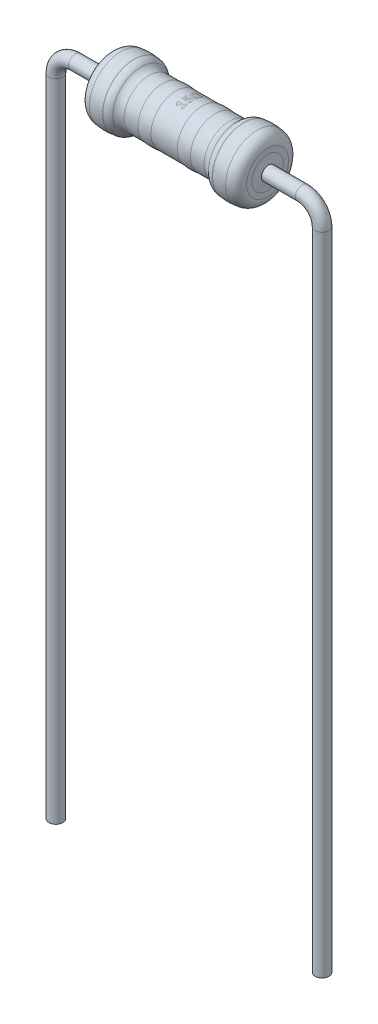
SolidWorks part; units mm, degrees
material "Plain Carbon Steel"
ref_plane "Front Plane" through (0, 0, 0) normal (0, 0, 1) x (1, 0, 0)
ref_plane "Top Plane" through (0, 0, 0) normal (0, 1, 0) x (1, 0, 0)
ref_plane "Right Plane" through (0, 0, 0) normal (1, 0, 0) x (0, 0, -1)
sketch "Sketch1" plane through (0, 0, 0) normal (0, 0, 1) x (1, 0, 0)
  line L0 (-4.33, 0) -> (4.33, 0)
  line L1 (-5.08, -0.75) -> (-5.08, -25.4)
  line L2 (5.08, -0.75) -> (5.08, -25.4)
  line L3 (-5.08, -25.4) -> (5.08, -25.4) construction
  line L4 (0, 0) -> (0, -25.4) construction
  arc A0 (-4.33, 0) -> (-5.08, -0.75) centre (-4.33, -0.75) ccw
  arc A1 (4.33, 0) -> (5.08, -0.75) centre (4.33, -0.75) cw
  dimension "D2" = 0.75
  dimension "D1" = 10.16
  dimension "D3" = 25.4
ref_plane "Plane1" through (-5.08, -25.4, 0) normal (0, -1, 0) x (-1, 0, 0)
sketch "Sketch2" plane through (-5.08, -25.4, 0) normal (0, -1, 0) x (-1, 0, 0)
  circle A0 centre (0, 0) radius 0.265
  dimension "D1" = 0.53
sweep "Sweep1" add profiles "Sketch2" path "Sketch1"
sketch "Sketch3" plane through (0, 0, 0) normal (0, 0, 1) x (1, 0, 0)
  line L0 (-3, 0) -> (3, 0)
  line L5 (-3, 0) -> (-3, 1.2)
  line L6 (3, 0) -> (3, 1.2)
  line L7 (-3, 1.2) -> (-1.75, 1.2)
  line L8 (3, 1.2) -> (1.75, 1.2)
  line L9 (-1.75, 1.2) -> (-1.75, 0.95)
  line L10 (-1.75, 0.95) -> (1.75, 0.95)
  line L11 (1.75, 0.95) -> (1.75, 1.2)
  line L12 (0, 0) -> (0, 0.95) construction
  dimension "D1" = 6
  dimension "D2" = 1.2
  dimension "D3" = 3.5
  dimension "D4" = 0.95
  dimension "D5" = 0.25
revolve "Revolve1" add sketch "Sketch3" angle 360 about L0
fillet "Fillet-1" radius 0.35 2 edges at (1.75, 0, 1.2) (-1.75, 0, 1.2)
fillet "Fillet-2" radius 0.4 4 edges at (3, 0, 1.2) (-3, 0, 1.2) (1.75, 0, 0.95) (-1.75, 0, 0.95)
sketch "Sketch5" plane through (0, 0, 0) normal (0, 0, 1) x (1, 0, 0)
  line L16 (-3, 0) -> (3, 0) construction
  line L17 (-2.6, 1.2) -> (-2.1, 1.2) construction
  line L18 (-2.6, 1.2) -> (-2.6, 0)
  line L19 (-2.6, 0) -> (-2.1, 0)
  line L20 (-2.1, 1.2) -> (-2.1, 0)
  line L21 (-1.75, 0.95) -> (1.75, 0.95) construction
  line L22 (2.6, 1.2) -> (2.1, 1.2) construction
  line L23 (2.6, 1.2) -> (2.6, 0)
  line L24 (2.6, 0) -> (2.1, 0)
  line L25 (2.1, 1.2) -> (2.1, 0)
  line L26 (-0.5, 0.95) -> (-1, 0.95) construction
  line L27 (-0.5, 0.95) -> (-0.5, 0)
  line L28 (-0.5, 0) -> (-1, 0)
  line L29 (-1, 0.95) -> (-1, 0)
  line L30 (-2.35, 1.2) -> (-2.35, 1.22) construction
  line L31 (1, 0.95) -> (0.5, 0.95) construction
  line L32 (1, 0.95) -> (1, 0)
  line L33 (1, 0) -> (0.5, 0)
  line L34 (0.5, 0.95) -> (0.5, 0)
  line L35 (-0.75, 0.95) -> (-0.75, 0.97) construction
  line L36 (0.75, 0.95) -> (0.75, 0.97) construction
  line L37 (2.35, 1.2) -> (2.35, 1.22) construction
  line L48 (-3, 0) -> (-3, 0.6)
  line L49 (-3, 0) -> (-3, 1.2) construction
  line L50 (-3, 0) -> (-3.05, 0)
  line L51 (-3.05, 0) -> (-3.05, 0.2)
  line L52 (3, 0) -> (3.05, 0)
  line L53 (3.05, 0) -> (3.05, 0.2)
  line L54 (3, 0) -> (3, 0.6)
  line L55 (3, 0) -> (3, 1.2) construction
  arc A0 (-2.6, 1.2) -> (-2.1, 1.2) centre (-2.35, -0.3525) cw
  arc A1 (-1, 0.95) -> (-0.5, 0.95) centre (-0.75, -0.6025) cw
  arc A2 (0.5, 0.95) -> (1, 0.95) centre (0.75, -0.6025) cw
  arc A3 (2.1, 1.2) -> (2.6, 1.2) centre (2.35, -0.3525) cw
  arc A6 (-3, 0.6) -> (-3.05, 0.2) centre (-4.625, 0.6) cw
  arc A7 (3.05, 0.2) -> (3, 0.6) centre (4.625, 0.6) cw
  dimension "D4" = 0.02
  dimension "D5" = 0.05
  dimension "D7" = 0.6
  dimension "D1" = 0.5
  dimension "D2" = 0.5
  dimension "D3" = 0.5
  dimension "D6" = 0.2
revolve "Revolve3" add sketch "Sketch5" angle 360 about L19
ref_plane "Plane2" through (0, 2, 0) normal (0, 1, 0) x (1, 0, 0)
sketch "Sketch6" plane through (0, 2, 0) normal (0, 1, 0) x (1, 0, 0)
  line L0 (0, 0) -> (0.15, 0) construction
  line L1 (0.15, 0.95) -> (0.15, -0.95) construction
  line L2 (0.5, 0.95) -> (-0.5, 0.95) construction
  text T0 "15Ω" font "Calibri" height 0.3
  dimension "D1" = 0.15
wrap "Wrap1" sketch "Sketch6" wrap type scribe source sketch "Sketch6" face at (-0.5, -0.95, 0)
